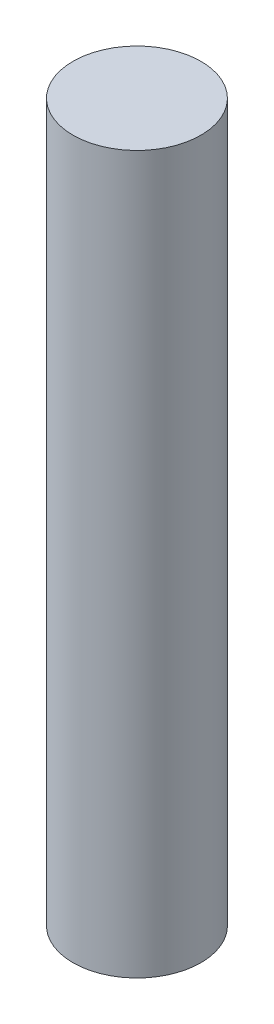
SolidWorks part; units mm, degrees
ref_plane "Front Plane" through (0, 0, 0) normal (0, 0, 1) x (1, 0, 0)
ref_plane "Top Plane" through (0, 0, 0) normal (0, 1, 0) x (1, 0, 0)
ref_plane "Right Plane" through (0, 0, 0) normal (1, 0, 0) x (0, 0, -1)
sketch "Sketch1" plane through (0, 0, 0) normal (0, 1, 0) x (1, 0, 0)
  circle A0 centre (0, 0) radius 3.175
  dimension "D1" = 6.35
extrude "Boss-Extrude1" add sketch "Sketch1" along normal blind 35.56
